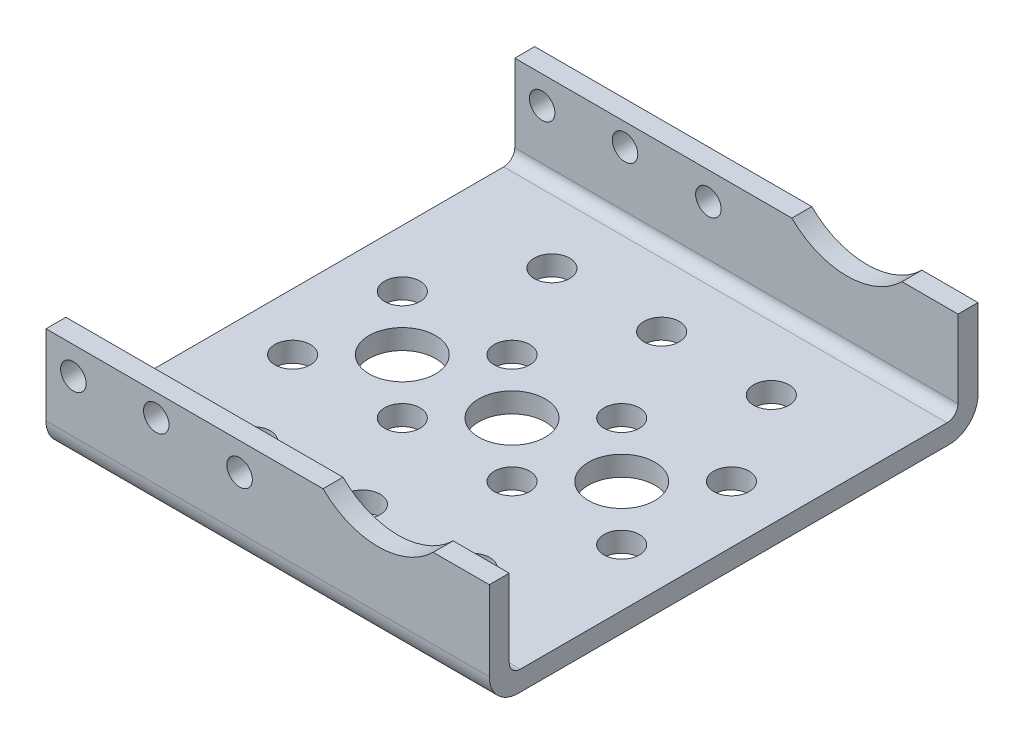
SolidWorks part; units mm, degrees
ref_plane "Front Plane" through (0, 0, 0) normal (0, 0, 1) x (1, 0, 0)
ref_plane "Top Plane" through (0, 0, 0) normal (0, 1, 0) x (1, 0, 0)
ref_plane "Right Plane" through (0, 0, 0) normal (1, 0, 0) x (0, 0, -1)
sketch "Model" plane through (0, 0, 0) normal (0, 0, 1) x (1, 0, 0)
  line L0 (23791.711, 2039.6293) -> (23791.711, 2044.2834)
  line L1 (23790.4383, 2043.5486) -> (23790.4383, 2039.0578)
  line L2 (23762.3662, 2020.5643) -> (23789.8726, 2036.445)
  line L3 (23789.7312, 2037.8331) -> (23762.5077, 2022.1157)
  line L4 (23781.1044, 2051.6318) -> (23764.4873, 2061.2254)
  line L5 (23790.6504, 2046.1205) -> (23788.1324, 2047.5742)
  line L6 (23779.8316, 2050.8969) -> (23763.2145, 2060.4906)
  line L7 (23789.3776, 2045.3857) -> (23786.8597, 2046.8394)
  line L8 (23790.4383, 2043.5486) -> (23791.711, 2044.2834)
  line L9 (23760.5278, 2026.2798) -> (23761.8006, 2027.0147)
  line L10 (23789.3776, 2045.3857) -> (23790.6504, 2046.1205)
  line L11 (23759.4671, 2028.117) -> (23760.7399, 2028.8518)
  line L12 (23786.8597, 2046.8394) -> (23788.1324, 2047.5742)
  line L13 (23756.9492, 2029.5706) -> (23758.222, 2030.3055)
  line L14 (23762.1539, 2055.3874) -> (23790.4383, 2039.0578)
  line L15 (23761.4468, 2054.1627) -> (23789.7312, 2037.8331)
  line L16 (23751.1939, 2034.363) -> (23749.9211, 2033.6282)
  line L17 (23781.1044, 2051.6318) -> (23779.8316, 2050.8969)
  line L18 (23762.1539, 2055.3874) -> (23762.1539, 2059.8782)
  line L19 (23761.8006, 2022.5239) -> (23761.8006, 2027.0147)
  line L20 (23760.5278, 2021.6258) -> (23760.5278, 2026.2798)
  line L21 (23739.1731, 2041.3031) -> (23761.4468, 2054.1627)
  line L22 (23763.2145, 2060.4906) -> (23764.4873, 2061.2254)
  line L23 (23733.304, 2043.2219) -> (23734.5768, 2043.9567)
  line L24 (23758.222, 2030.3055) -> (23760.7399, 2028.8518)
  line L25 (23734.5768, 2043.9567) -> (23751.1939, 2034.363)
  line L26 (23762.4645, 2060.5649) -> (23763.7373, 2061.2997)
  line L27 (23732.554, 2043.2961) -> (23733.8268, 2044.031)
  line L28 (23756.9492, 2029.5706) -> (23759.4671, 2028.117)
  line L29 (23733.304, 2043.2219) -> (23749.9211, 2033.6282)
  line L30 (23761.8006, 2022.5239) -> (23762.5077, 2022.1157)
  line L31 (23760.5278, 2021.6258) -> (23732.2434, 2037.9554)
  line L32 (23761.0663, 2020.4355) -> (23732.7819, 2036.7652)
  line L33 (23732.2434, 2037.9554) -> (23732.2434, 2042.6095)
  line L60 (23618.6723, 1978.7528) -> (23578.6723, 1978.7528)
  line L61 (23618.6723, 1976.1528) -> (23578.6723, 1976.1528)
  line L62 (23618.6723, 1978.7528) -> (23618.6723, 1934.6528)
  line L63 (23618.6723, 1937.2528) -> (23578.6723, 1937.2528)
  line L64 (23578.6723, 1934.6528) -> (23578.6723, 1978.7528)
  line L65 (23618.6723, 1934.6528) -> (23578.6723, 1934.6528)
  circle A21 centre (23588.7728, 1943.2028) radius 1.6
  circle A22 centre (23598.6723, 1943.2028) radius 1.6
  circle A23 centre (23608.5718, 1943.2028) radius 1.6
  circle A24 centre (23613.5215, 1951.7531) radius 1.6
  circle A25 centre (23603.622, 1951.7531) radius 1.6
  circle A26 centre (23593.7225, 1951.7531) radius 1.6
  circle A27 centre (23583.8231, 1951.7531) radius 1.6
  circle A28 centre (23583.8231, 1961.6526) radius 1.6
  circle A29 centre (23593.7225, 1961.6526) radius 1.6
  circle A30 centre (23603.622, 1961.6526) radius 1.6
  circle A31 centre (23613.5215, 1961.6526) radius 1.6
  circle A32 centre (23608.5718, 1970.2028) radius 1.6
  circle A33 centre (23598.6723, 1970.2028) radius 1.6
  circle A34 centre (23588.7728, 1970.2028) radius 1.6
  circle A35 centre (23588.7728, 1956.7028) radius 3
  circle A36 centre (23608.5718, 1956.7028) radius 3
  circle A37 centre (23598.6723, 1956.7028) radius 3
  spline S0 degree 3 poles (23760.8459, 2034.751) (23760.9643, 2034.8193) (23761.2325, 2034.93) (23761.6695, 2035.0174) (23762.1318, 2035.0302) (23762.5815, 2034.967) (23762.9823, 2034.8332) (23763.261, 2034.6635) (23763.4246, 2034.4993) (23763.5115, 2034.3715) (23763.565, 2034.2367) (23763.5772, 2034.1433) (23763.5772, 2034.0978) knots 0 0 0 0 0.128688 0.270271 0.417431 0.561777 0.695448 0.812714 0.864677 0.912512 0.95714 1 1 1 1
  spline S1 degree 3 poles (23746.3772, 2042.1805) (23746.3772, 2042.2415) (23746.3997, 2042.3685) (23746.496, 2042.5455) (23746.6482, 2042.7055) (23746.7756, 2042.7932) (23746.8458, 2042.8337) knots 0 0 0 0 0.217784 0.450913 0.710298 1 1 1 1
  spline S2 degree 3 poles (23770.3917, 2044.3037) (23770.5102, 2044.372) (23770.7783, 2044.4827) (23771.2154, 2044.5701) (23771.6776, 2044.5829) (23772.1274, 2044.5197) (23772.5282, 2044.3859) (23772.8069, 2044.2162) (23772.9705, 2044.052) (23773.0574, 2043.9242) (23773.1109, 2043.7894) (23773.1231, 2043.696) (23773.1231, 2043.6505) knots 0 0 0 0 0.128688 0.270271 0.417431 0.561777 0.695448 0.812714 0.864677 0.912512 0.95714 1 1 1 1
  spline S3 degree 3 poles (23788.0742, 2044.7771) (23788.0362, 2044.7552) (23787.9652, 2044.6956) (23787.8895, 2044.572) (23787.8446, 2044.4197) (23787.8358, 2044.3088) (23787.8358, 2044.2505) knots 0 0 0 0 0.217775 0.450893 0.710352 1 1 1 1
  spline S4 degree 3 poles (23753.8458, 2038.7923) (23753.9643, 2038.8607) (23754.2324, 2038.9714) (23754.6695, 2039.0588) (23755.1317, 2039.0716) (23755.5815, 2039.0084) (23755.9823, 2038.8745) (23756.261, 2038.7049) (23756.4246, 2038.5407) (23756.5115, 2038.4129) (23756.565, 2038.2781) (23756.5772, 2038.1847) (23756.5772, 2038.1392) knots 0 0 0 0 0.128688 0.270271 0.417431 0.561777 0.695448 0.812714 0.864677 0.912512 0.95714 1 1 1 1
  spline S5 degree 3 poles (23744.0215, 2035.6732) (23743.9835, 2035.6513) (23743.9125, 2035.5917) (23743.8368, 2035.4681) (23743.792, 2035.3158) (23743.7831, 2035.2049) (23743.7831, 2035.1466) knots 0 0 0 0 0.217775 0.450893 0.710352 1 1 1 1
  spline S6 degree 3 poles (23771.0985, 2035.3225) (23771.2302, 2035.2465) (23771.4691, 2035.082) (23771.7545, 2034.7823) (23771.9076, 2034.4998) (23771.9674, 2034.2695) (23771.9772, 2034.1546) (23771.9772, 2034.0978) knots 0 0 0 0 0.289555 0.548652 0.781634 0.891841 1 1 1 1
  spline S7 degree 3 poles (23758.1637, 2027.5084) (23758.1257, 2027.4865) (23758.0547, 2027.4269) (23757.979, 2027.3033) (23757.9342, 2027.151) (23757.9253, 2027.0401) (23757.9253, 2026.9818) knots 0 0 0 0 0.217775 0.450893 0.710352 1 1 1 1
  spline S8 degree 3 poles (23773.932, 2052.9419) (23773.894, 2052.92) (23773.823, 2052.8604) (23773.7473, 2052.7368) (23773.7024, 2052.5845) (23773.6936, 2052.4736) (23773.6936, 2052.4154) knots 0 0 0 0 0.217775 0.450893 0.710352 1 1 1 1
  spline S9 degree 3 poles (23746.8458, 2042.8337) (23746.9642, 2042.9021) (23747.2324, 2043.0127) (23747.6694, 2043.1002) (23748.1317, 2043.113) (23748.5815, 2043.0498) (23748.9822, 2042.9159) (23749.261, 2042.7463) (23749.4245, 2042.5821) (23749.5115, 2042.4543) (23749.565, 2042.3194) (23749.5772, 2042.2261) (23749.5772, 2042.1805) knots 0 0 0 0 0.128688 0.270271 0.417431 0.561777 0.695448 0.812714 0.864677 0.912512 0.95714 1 1 1 1
  spline S10 degree 3 poles (23753.3772, 2038.1392) (23753.3772, 2038.2001) (23753.3997, 2038.3271) (23753.496, 2038.5041) (23753.6483, 2038.6641) (23753.7756, 2038.7518) (23753.8458, 2038.7923) knots 0 0 0 0 0.217784 0.450913 0.710298 1 1 1 1
  spline S11 degree 3 poles (23763.3917, 2048.345) (23763.5101, 2048.4134) (23763.7783, 2048.5241) (23764.2153, 2048.6115) (23764.6776, 2048.6243) (23765.1274, 2048.5611) (23765.5281, 2048.4272) (23765.8069, 2048.2576) (23765.9704, 2048.0934) (23766.0574, 2047.9656) (23766.1109, 2047.8308) (23766.1231, 2047.7374) (23766.1231, 2047.6918) knots 0 0 0 0 0.128688 0.270271 0.417431 0.561777 0.695448 0.812714 0.864677 0.912512 0.95714 1 1 1 1
  spline S12 degree 3 poles (23760.3772, 2034.0978) (23760.3772, 2034.1587) (23760.3998, 2034.2857) (23760.4961, 2034.4627) (23760.6483, 2034.6227) (23760.7757, 2034.7104) (23760.8459, 2034.751) knots 0 0 0 0 0.217784 0.450913 0.710298 1 1 1 1
  spline S13 degree 3 poles (23739.8536, 2037.1593) (23739.8252, 2037.143) (23739.7627, 2037.1171) (23739.6596, 2037.102) (23739.5488, 2037.1102) (23739.3878, 2037.1531) (23739.1821, 2037.2656) (23738.9548, 2037.467) (23738.7538, 2037.7242) (23738.5957, 2038.0165) (23738.4931, 2038.3199) (23738.4656, 2038.5266) (23738.4656, 2038.6249) knots 0 0 0 0 0.042861 0.087494 0.135333 0.187304 0.304578 0.438252 0.582594 0.729744 0.871324 1 1 1 1
  spline S14 degree 3 poles (23733.4148, 2041.7968) (23733.3769, 2041.7749) (23733.3058, 2041.7153) (23733.2302, 2041.5917) (23733.1853, 2041.4394) (23733.1765, 2041.3285) (23733.1765, 2041.2702) knots 0 0 0 0 0.217775 0.450893 0.710352 1 1 1 1
  spline S15 degree 3 poles (23763.3253, 2059.0655) (23763.2874, 2059.0436) (23763.2163, 2058.984) (23763.1407, 2058.8604) (23763.0958, 2058.7081) (23763.0869, 2058.5973) (23763.0869, 2058.539) knots 0 0 0 0 0.217775 0.450893 0.710352 1 1 1 1
  spline S16 degree 3 poles (23786.8597, 2046.8394) (23786.744, 2046.7739) (23786.4986, 2046.6615) (23786.1022, 2046.5546) (23785.6799, 2046.5098) (23785.0726, 2046.5334) (23784.2661, 2046.7294) (23783.2983, 2047.1908) (23782.3352, 2047.8651) (23781.4109, 2048.7274) (23780.5586, 2049.7462) (23780.0613, 2050.5018) (23779.8316, 2050.8969) knots 0 0 0 0 0.045082 0.091075 0.138692 0.188569 0.296642 0.417359 0.550403 0.693911 0.844959 1 1 1 1
  spline S17 degree 3 poles (23769.7641, 2054.4281) (23769.7357, 2054.4117) (23769.6732, 2054.3858) (23769.57, 2054.3707) (23769.4593, 2054.3789) (23769.2983, 2054.4218) (23769.0926, 2054.5343) (23768.8652, 2054.7357) (23768.6643, 2054.9929) (23768.5062, 2055.2852) (23768.4036, 2055.5887) (23768.3761, 2055.7953) (23768.3761, 2055.8936) knots 0 0 0 0 0.042861 0.087494 0.135333 0.187304 0.304578 0.438252 0.582594 0.729744 0.871324 1 1 1 1
  spline S18 degree 3 poles (23763.2145, 2060.4906) (23763.1487, 2060.5286) (23763.0178, 2060.5909) (23762.8165, 2060.6395) (23762.6277, 2060.6347) (23762.514, 2060.5934) (23762.4645, 2060.5649) knots 0 0 0 0 0.289699 0.549083 0.782213 1 1 1 1
  spline S19 degree 3 poles (23767.3773, 2030.0564) (23767.3773, 2030.1173) (23767.3998, 2030.2444) (23767.4961, 2030.4213) (23767.6483, 2030.5813) (23767.7757, 2030.6691) (23767.8459, 2030.7096) knots 0 0 0 0 0.217784 0.450913 0.710298 1 1 1 1
  spline S20 degree 3 poles (23753.8458, 2046.8751) (23753.9642, 2046.9435) (23754.2324, 2047.0542) (23754.6694, 2047.1416) (23755.1317, 2047.1544) (23755.5814, 2047.0912) (23755.9822, 2046.9573) (23756.2609, 2046.7877) (23756.4245, 2046.6235) (23756.5114, 2046.4957) (23756.5649, 2046.3609) (23756.5772, 2046.2675) (23756.5772, 2046.2219) knots 0 0 0 0 0.128688 0.270271 0.417431 0.561777 0.695448 0.812714 0.864677 0.912512 0.95714 1 1 1 1
  spline S21 degree 3 poles (23762.9231, 2047.6918) (23762.9231, 2047.7528) (23762.9456, 2047.8798) (23763.0419, 2048.0568) (23763.1941, 2048.2168) (23763.3215, 2048.3045) (23763.3917, 2048.345) knots 0 0 0 0 0.217784 0.450913 0.710298 1 1 1 1
  spline S22 degree 3 poles (23758.9772, 2038.1391) (23758.9772, 2038.2245) (23759, 2038.3996) (23759.1004, 2038.6524) (23759.2634, 2038.892) (23759.4842, 2039.1138) (23759.7578, 2039.3138) (23760.1986, 2039.5534) (23760.8445, 2039.7691) (23761.6873, 2039.8875) (23762.5542, 2039.8635) (23763.3736, 2039.6996) (23763.8764, 2039.4921) (23764.0985, 2039.3639) knots 0 0 0 0 0.042846 0.087464 0.135285 0.187234 0.243726 0.304732 0.438366 0.582673 0.729791 0.871341 1 1 1 1
  spline S23 degree 3 poles (23790.4383, 2043.5486) (23790.4383, 2043.6324) (23790.4229, 2043.8069) (23790.3395, 2044.1651) (23790.1458, 2044.6045) (23789.8622, 2044.9919) (23789.5936, 2045.2432) (23789.4502, 2045.3438) (23789.3776, 2045.3857) knots 0 0 0 0 0.114224 0.237557 0.500001 0.762445 0.885777 1 1 1 1
  spline S24 degree 3 poles (23764.0985, 2039.3639) (23764.2302, 2039.2879) (23764.469, 2039.1234) (23764.7544, 2038.8237) (23764.9076, 2038.5412) (23764.9673, 2038.3109) (23764.9772, 2038.196) (23764.9772, 2038.1392) knots 0 0 0 0 0.289555 0.548652 0.781634 0.891841 1 1 1 1
  spline S25 degree 3 poles (23768.3761, 2055.8936) (23768.3761, 2055.9519) (23768.385, 2056.0627) (23768.4299, 2056.215) (23768.5055, 2056.3386) (23768.5766, 2056.3982) (23768.6145, 2056.4201) knots 0 0 0 0 0.289648 0.549107 0.782225 1 1 1 1
  spline S26 degree 3 poles (23769.9231, 2043.6505) (23769.9231, 2043.7114) (23769.9456, 2043.8384) (23770.0419, 2044.0154) (23770.1942, 2044.1754) (23770.3215, 2044.2631) (23770.3917, 2044.3037) knots 0 0 0 0 0.217784 0.450913 0.710298 1 1 1 1
  spline S27 degree 3 poles (23765.9773, 2034.0978) (23765.9773, 2034.1832) (23766.0001, 2034.3582) (23766.1005, 2034.611) (23766.2634, 2034.8507) (23766.4842, 2035.0724) (23766.7578, 2035.2724) (23767.1986, 2035.512) (23767.8445, 2035.7278) (23768.6873, 2035.8461) (23769.5542, 2035.8221) (23770.3736, 2035.6582) (23770.8765, 2035.4507) (23771.0985, 2035.3225) knots 0 0 0 0 0.042846 0.087464 0.135285 0.187234 0.243726 0.304732 0.438366 0.582673 0.729791 0.871341 1 1 1 1
  spline S28 degree 3 poles (23787.8358, 2044.2505) (23787.8358, 2044.1523) (23787.8633, 2043.9456) (23787.9659, 2043.6422) (23788.124, 2043.3499) (23788.3249, 2043.0927) (23788.5522, 2042.8913) (23788.758, 2042.7787) (23788.9189, 2042.7359) (23789.0297, 2042.7277) (23789.1329, 2042.7427) (23789.1954, 2042.7687) (23789.2237, 2042.785) knots 0 0 0 0 0.128676 0.270256 0.417406 0.561748 0.695422 0.812696 0.864667 0.912506 0.957139 1 1 1 1
  spline S29 degree 3 poles (23760.8458, 2042.8338) (23760.9642, 2042.9021) (23761.2324, 2043.0128) (23761.6694, 2043.1002) (23762.1317, 2043.113) (23762.5815, 2043.0498) (23762.9822, 2042.916) (23763.261, 2042.7463) (23763.4245, 2042.5821) (23763.5115, 2042.4543) (23763.565, 2042.3195) (23763.5772, 2042.2261) (23763.5772, 2042.1806) knots 0 0 0 0 0.128688 0.270271 0.417431 0.561777 0.695448 0.812714 0.864677 0.912512 0.95714 1 1 1 1
  spline S30 degree 3 poles (23773.6936, 2052.4154) (23773.6936, 2052.3171) (23773.7211, 2052.1104) (23773.8237, 2051.807) (23773.9818, 2051.5147) (23774.1827, 2051.2575) (23774.41, 2051.0561) (23774.6158, 2050.9436) (23774.7767, 2050.9007) (23774.8875, 2050.8925) (23774.9907, 2050.9076) (23775.0532, 2050.9335) (23775.0815, 2050.9498) knots 0 0 0 0 0.128676 0.270256 0.417406 0.561748 0.695422 0.812696 0.864667 0.912506 0.957139 1 1 1 1
  spline S31 degree 3 poles (23776.9231, 2039.6091) (23776.9231, 2039.67) (23776.9457, 2039.7971) (23777.042, 2039.974) (23777.1942, 2040.134) (23777.3216, 2040.2217) (23777.3918, 2040.2623) knots 0 0 0 0 0.217784 0.450913 0.710298 1 1 1 1
  spline S32 degree 3 poles (23751.9772, 2042.1805) (23751.9772, 2042.2659) (23752, 2042.441) (23752.1004, 2042.6938) (23752.2634, 2042.9334) (23752.4841, 2043.1552) (23752.7578, 2043.3551) (23753.1986, 2043.5948) (23753.8445, 2043.8105) (23754.6873, 2043.9289) (23755.5541, 2043.9049) (23756.3736, 2043.741) (23756.8764, 2043.5335) (23757.0985, 2043.4053) knots 0 0 0 0 0.042846 0.087464 0.135285 0.187234 0.243726 0.304732 0.438366 0.582673 0.729791 0.871341 1 1 1 1
  spline S33 degree 3 poles (23790.4383, 2039.0578) (23790.4383, 2038.9419) (23790.3948, 2038.6974) (23790.2432, 2038.3539) (23790.0215, 2038.0509) (23789.8315, 2037.891) (23789.7312, 2037.8331) knots 0 0 0 0 0.237239 0.500002 0.762764 1 1 1 1
  spline S34 degree 3 poles (23762.5077, 2022.1157) (23762.4638, 2022.0903) (23762.3765, 2022.0488) (23762.2423, 2022.0164) (23762.1164, 2022.0196) (23762.0406, 2022.0471) (23762.0077, 2022.0661) knots 0 0 0 0 0.2897 0.549084 0.782214 1 1 1 1
  spline S35 degree 3 poles (23774.3772, 2034.0978) (23774.3772, 2034.1588) (23774.3998, 2034.2858) (23774.4961, 2034.4628) (23774.6483, 2034.6227) (23774.7757, 2034.7105) (23774.8459, 2034.751) knots 0 0 0 0 0.217784 0.450913 0.710298 1 1 1 1
  spline S36 degree 3 poles (23760.5278, 2026.2798) (23760.5278, 2026.3637) (23760.5124, 2026.5382) (23760.429, 2026.8964) (23760.2353, 2027.3357) (23759.9517, 2027.7232) (23759.6831, 2027.9745) (23759.5397, 2028.075) (23759.4671, 2028.117) knots 0 0 0 0 0.114224 0.237557 0.500001 0.762445 0.885777 1 1 1 1
  spline S37 degree 3 poles (23756.9492, 2029.5706) (23756.8335, 2029.5052) (23756.5881, 2029.3928) (23756.1917, 2029.2859) (23755.7694, 2029.2411) (23755.1621, 2029.2646) (23754.3556, 2029.4607) (23753.3878, 2029.9221) (23752.4247, 2030.5963) (23751.5005, 2031.4587) (23750.6481, 2032.4775) (23750.1508, 2033.2331) (23749.9211, 2033.6282) knots 0 0 0 0 0.045082 0.091074 0.138691 0.188569 0.296642 0.417359 0.550403 0.693912 0.844959 1 1 1 1
  spline S38 degree 3 poles (23733.304, 2043.2219) (23733.2382, 2043.2599) (23733.1073, 2043.3222) (23732.906, 2043.3708) (23732.7172, 2043.366) (23732.6035, 2043.3247) (23732.554, 2043.2961) knots 0 0 0 0 0.289699 0.549083 0.782213 1 1 1 1
  spline S39 degree 3 poles (23738.4656, 2038.6249) (23738.4656, 2038.6831) (23738.4745, 2038.794) (23738.5194, 2038.9463) (23738.595, 2039.0699) (23738.6661, 2039.1295) (23738.704, 2039.1514) knots 0 0 0 0 0.289648 0.549107 0.782225 1 1 1 1
  spline S40 degree 3 poles (23757.9253, 2026.9818) (23757.9253, 2026.8835) (23757.9528, 2026.6769) (23758.0554, 2026.3735) (23758.2135, 2026.0812) (23758.4144, 2025.8239) (23758.6417, 2025.6226) (23758.8475, 2025.51) (23759.0084, 2025.4672) (23759.1192, 2025.4589) (23759.2224, 2025.474) (23759.2849, 2025.4999) (23759.3132, 2025.5163) knots 0 0 0 0 0.128676 0.270256 0.417406 0.561748 0.695422 0.812696 0.864667 0.912506 0.957139 1 1 1 1
  spline S41 degree 3 poles (23743.7831, 2035.1466) (23743.7831, 2035.0484) (23743.8106, 2034.8417) (23743.9132, 2034.5383) (23744.0713, 2034.246) (23744.2722, 2033.9888) (23744.4995, 2033.7874) (23744.7053, 2033.6748) (23744.8662, 2033.632) (23744.977, 2033.6238) (23745.0802, 2033.6388) (23745.1427, 2033.6648) (23745.1711, 2033.6811) knots 0 0 0 0 0.128676 0.270256 0.417406 0.561748 0.695422 0.812696 0.864667 0.912506 0.957139 1 1 1 1
  spline S42 degree 3 poles (23733.1765, 2041.2702) (23733.1765, 2041.172) (23733.2039, 2040.9653) (23733.3065, 2040.6619) (23733.4647, 2040.3696) (23733.6656, 2040.1124) (23733.8929, 2039.911) (23734.0986, 2039.7984) (23734.2596, 2039.7556) (23734.3704, 2039.7474) (23734.4735, 2039.7624) (23734.5361, 2039.7884) (23734.5644, 2039.8047) knots 0 0 0 0 0.128676 0.270256 0.417406 0.561748 0.695422 0.812696 0.864667 0.912506 0.957139 1 1 1 1
  spline S43 degree 3 poles (23763.0869, 2058.539) (23763.0869, 2058.4407) (23763.1144, 2058.2341) (23763.217, 2057.9306) (23763.3751, 2057.6383) (23763.5761, 2057.3811) (23763.8034, 2057.1797) (23764.0091, 2057.0672) (23764.1701, 2057.0243) (23764.2809, 2057.0161) (23764.384, 2057.0312) (23764.4465, 2057.0571) (23764.4749, 2057.0735) knots 0 0 0 0 0.128676 0.270256 0.417406 0.561748 0.695422 0.812696 0.864667 0.912506 0.957139 1 1 1 1
  spline S44 degree 3 poles (23767.8458, 2038.7924) (23767.9643, 2038.8608) (23768.2324, 2038.9714) (23768.6695, 2039.0588) (23769.1317, 2039.0716) (23769.5815, 2039.0084) (23769.9823, 2038.8746) (23770.261, 2038.7049) (23770.4246, 2038.5407) (23770.5115, 2038.4129) (23770.565, 2038.2781) (23770.5772, 2038.1847) (23770.5772, 2038.1392) knots 0 0 0 0 0.128688 0.270271 0.417431 0.561777 0.695448 0.812714 0.864677 0.912512 0.95714 1 1 1 1
  spline S45 degree 3 poles (23767.3772, 2038.1392) (23767.3772, 2038.2001) (23767.3997, 2038.3272) (23767.496, 2038.5041) (23767.6483, 2038.6641) (23767.7756, 2038.7518) (23767.8458, 2038.7924) knots 0 0 0 0 0.217784 0.450913 0.710298 1 1 1 1
  spline S46 degree 3 poles (23760.5278, 2021.6258) (23760.5278, 2021.494) (23760.5477, 2021.2435) (23760.6492, 2020.8993) (23760.82, 2020.6199) (23760.9805, 2020.4851) (23761.0663, 2020.4355) knots 0 0 0 0 0.289773 0.549065 0.782224 1 1 1 1
  spline S47 degree 3 poles (23760.3772, 2042.1806) (23760.3772, 2042.2415) (23760.3997, 2042.3685) (23760.496, 2042.5455) (23760.6482, 2042.7055) (23760.7756, 2042.7932) (23760.8458, 2042.8338) knots 0 0 0 0 0.217784 0.450913 0.710298 1 1 1 1
  spline S48 degree 3 poles (23745.6265, 2037.5861) (23745.7973, 2037.574) (23746.1213, 2037.5207) (23746.4933, 2037.3746) (23746.7325, 2037.214) (23746.8703, 2037.0826) (23746.9695, 2036.9388) (23747.0083, 2036.8338) (23747.0193, 2036.782) knots 0 0 0 0 0.301153 0.573738 0.695218 0.805891 0.906674 1 1 1 1
  spline S49 degree 3 poles (23774.8459, 2034.751) (23774.9643, 2034.8194) (23775.2325, 2034.93) (23775.6695, 2035.0175) (23776.1318, 2035.0303) (23776.5815, 2034.9671) (23776.9823, 2034.8332) (23777.261, 2034.6635) (23777.4246, 2034.4994) (23777.5115, 2034.3716) (23777.565, 2034.2367) (23777.5772, 2034.1434) (23777.5772, 2034.0978) knots 0 0 0 0 0.128688 0.270271 0.417431 0.561777 0.695448 0.812714 0.864677 0.912512 0.95714 1 1 1 1
  spline S50 degree 3 poles (23751.7739, 2033.4701) (23751.8985, 2033.5025) (23752.157, 2033.5474) (23752.5501, 2033.5585) (23752.9363, 2033.5142) (23753.2927, 2033.4174) (23753.5987, 2033.2732) (23753.837, 2033.0891) (23753.9705, 2032.9017) (23754.0227, 2032.7448) (23754.0313, 2032.6664) (23754.0313, 2032.6279) knots 0 0 0 0 0.144199 0.292657 0.439268 0.578198 0.704655 0.81588 0.912429 0.95686 1 1 1 1
  spline S51 degree 3 poles (23757.0985, 2043.4053) (23757.2302, 2043.3293) (23757.469, 2043.1647) (23757.7544, 2042.8651) (23757.9076, 2042.5826) (23757.9673, 2042.3523) (23757.9772, 2042.2374) (23757.9772, 2042.1806) knots 0 0 0 0 0.289555 0.548652 0.781634 0.891841 1 1 1 1
  spline S52 degree 3 poles (23753.3772, 2046.2219) (23753.3772, 2046.2829) (23753.3997, 2046.4099) (23753.496, 2046.5869) (23753.6482, 2046.7469) (23753.7756, 2046.8346) (23753.8458, 2046.8751) knots 0 0 0 0 0.217784 0.450913 0.710298 1 1 1 1
  spline S53 degree 3 poles (23760.8961, 2028.9582) (23760.9315, 2028.9116) (23760.9907, 2028.8139) (23761.0213, 2028.7032) (23761.0277, 2028.6491) knots 0 0 0 0 0.517744 1 1 1 1
  spline S54 degree 3 poles (23759.6265, 2029.5033) (23759.7608, 2029.4938) (23760.0201, 2029.4562) (23760.3786, 2029.3433) (23760.6778, 2029.1819) (23760.8365, 2029.0365) (23760.8961, 2028.9582) knots 0 0 0 0 0.285068 0.552072 0.791759 1 1 1 1
  spline S55 degree 3 poles (23777.3918, 2040.2623) (23777.5102, 2040.3307) (23777.7784, 2040.4413) (23778.2154, 2040.5287) (23778.6777, 2040.5415) (23779.1274, 2040.4783) (23779.5282, 2040.3445) (23779.8069, 2040.1748) (23779.9705, 2040.0106) (23780.0574, 2039.8828) (23780.1109, 2039.748) (23780.1231, 2039.6546) (23780.1231, 2039.6091) knots 0 0 0 0 0.128688 0.270271 0.417431 0.561777 0.695448 0.812714 0.864677 0.912512 0.95714 1 1 1 1
  spline S56 degree 3 poles (23767.8459, 2030.7096) (23767.9643, 2030.778) (23768.2325, 2030.8886) (23768.6695, 2030.976) (23769.1318, 2030.9888) (23769.5815, 2030.9256) (23769.9823, 2030.7918) (23770.2611, 2030.6221) (23770.4246, 2030.458) (23770.5115, 2030.3301) (23770.5651, 2030.1953) (23770.5773, 2030.102) (23770.5773, 2030.0564) knots 0 0 0 0 0.128688 0.270271 0.417431 0.561777 0.695448 0.812714 0.864677 0.912512 0.95714 1 1 1 1
  spline S57 degree 3 poles (23745.1711, 2033.6811) (23745.209, 2033.703) (23745.2801, 2033.7626) (23745.3557, 2033.8862) (23745.4006, 2034.0385) (23745.4094, 2034.1494) (23745.4094, 2034.2077) knots 0 0 0 0 0.217775 0.450893 0.710352 1 1 1 1
  spline S58 degree 3 poles (23775.0815, 2050.9498) (23775.1195, 2050.9717) (23775.1906, 2051.0313) (23775.2662, 2051.155) (23775.3111, 2051.3073) (23775.3199, 2051.4181) (23775.3199, 2051.4764) knots 0 0 0 0 0.217775 0.450893 0.710352 1 1 1 1
  spline S59 degree 3 poles (23789.2237, 2042.785) (23789.2617, 2042.8069) (23789.3328, 2042.8665) (23789.4084, 2042.9901) (23789.4533, 2043.1424) (23789.4621, 2043.2533) (23789.4621, 2043.3116) knots 0 0 0 0 0.217775 0.450893 0.710352 1 1 1 1
  spline S60 degree 3 poles (23734.5644, 2039.8047) (23734.6024, 2039.8266) (23734.6734, 2039.8862) (23734.7491, 2040.0098) (23734.7939, 2040.1621) (23734.8028, 2040.273) (23734.8028, 2040.3313) knots 0 0 0 0 0.217775 0.450893 0.710352 1 1 1 1
  spline S61 degree 3 poles (23759.3132, 2025.5163) (23759.3512, 2025.5382) (23759.4223, 2025.5978) (23759.4979, 2025.7214) (23759.5428, 2025.8737) (23759.5516, 2025.9846) (23759.5516, 2026.0429) knots 0 0 0 0 0.217775 0.450893 0.710352 1 1 1 1
  spline S62 degree 3 poles (23738.704, 2039.1514) (23738.7324, 2039.1678) (23738.7949, 2039.1937) (23738.8981, 2039.2088) (23739.0088, 2039.2006) (23739.1698, 2039.1577) (23739.3756, 2039.0451) (23739.6029, 2038.8438) (23739.8038, 2038.5865) (23739.9619, 2038.2942) (23740.0645, 2037.9908) (23740.092, 2037.7842) (23740.092, 2037.6859) knots 0 0 0 0 0.042861 0.087494 0.135333 0.187304 0.304578 0.438252 0.582594 0.729744 0.871324 1 1 1 1
  spline S63 degree 3 poles (23764.4749, 2057.0735) (23764.5129, 2057.0954) (23764.5839, 2057.155) (23764.6595, 2057.2786) (23764.7044, 2057.4309) (23764.7133, 2057.5417) (23764.7133, 2057.6) knots 0 0 0 0 0.217775 0.450893 0.710352 1 1 1 1
  spline S64 degree 3 poles (23768.6145, 2056.4201) (23768.6429, 2056.4365) (23768.7054, 2056.4624) (23768.8086, 2056.4775) (23768.9193, 2056.4693) (23769.0803, 2056.4264) (23769.286, 2056.3139) (23769.5134, 2056.1125) (23769.7143, 2055.8553) (23769.8724, 2055.563) (23769.975, 2055.2595) (23770.0025, 2055.0529) (23770.0025, 2054.9546) knots 0 0 0 0 0.042861 0.087494 0.135333 0.187304 0.304578 0.438252 0.582594 0.729744 0.871324 1 1 1 1
  spline S65 degree 3 poles (23732.7819, 2036.7652) (23732.6961, 2036.8147) (23732.5356, 2036.9496) (23732.3648, 2037.2289) (23732.2633, 2037.5731) (23732.2434, 2037.8236) (23732.2434, 2037.9554) knots 0 0 0 0 0.217776 0.450935 0.710227 1 1 1 1
  spline S66 degree 3 poles (23761.0663, 2020.4355) (23761.152, 2020.386) (23761.3491, 2020.3145) (23761.6764, 2020.3062) (23762.0252, 2020.3904) (23762.2521, 2020.4984) (23762.3662, 2020.5643) knots 0 0 0 0 0.217778 0.450937 0.710229 1 1 1 1
  spline S67 degree 3 poles (23762.0077, 2022.0661) (23761.9747, 2022.0852) (23761.913, 2022.1371) (23761.8473, 2022.2445) (23761.8082, 2022.3769) (23761.8006, 2022.4732) (23761.8006, 2022.5239) knots 0 0 0 0 0.217785 0.450914 0.710299 1 1 1 1
  spline S68 degree 3 poles (23764.69, 2037.409) (23764.6524, 2037.455) (23764.4793, 2037.644) (23764.2686, 2037.796) (23764.0985, 2037.8942) knots 0 0 0 0 0.232466 1 1 1 1
  spline S69 degree 3 poles (23764.9772, 2038.1392) (23764.9772, 2038.0538) (23764.9544, 2037.8787) (23764.854, 2037.6259) (23764.691, 2037.3863) (23764.4702, 2037.1645) (23764.1966, 2036.9646) (23763.7558, 2036.725) (23763.1099, 2036.5092) (23762.2671, 2036.3909) (23761.4002, 2036.4148) (23760.5808, 2036.5788) (23760.078, 2036.7862) (23759.8559, 2036.9144) knots 0 0 0 0 0.042846 0.087464 0.135285 0.187234 0.243726 0.304732 0.438366 0.582673 0.729791 0.871341 1 1 1 1
  spline S70 degree 3 poles (23766.1231, 2047.6918) (23766.1231, 2047.6309) (23766.1006, 2047.5039) (23766.0043, 2047.3269) (23765.852, 2047.1669) (23765.7247, 2047.0792) (23765.6545, 2047.0387) knots 0 0 0 0 0.217784 0.450913 0.710298 1 1 1 1
  spline S71 degree 3 poles (23771.69, 2033.3676) (23771.6524, 2033.4137) (23771.4793, 2033.6026) (23771.2686, 2033.7546) (23771.0985, 2033.8528) knots 0 0 0 0 0.232466 1 1 1 1
  spline S72 degree 3 poles (23771.9772, 2034.0978) (23771.9772, 2034.0124) (23771.9544, 2033.8374) (23771.854, 2033.5846) (23771.6911, 2033.3449) (23771.4703, 2033.1232) (23771.1966, 2032.9232) (23770.7558, 2032.6836) (23770.11, 2032.4678) (23769.2672, 2032.3495) (23768.4003, 2032.3734) (23767.5808, 2032.5374) (23767.078, 2032.7448) (23766.8559, 2032.8731) knots 0 0 0 0 0.042846 0.087464 0.135285 0.187234 0.243726 0.304732 0.438366 0.582673 0.729791 0.871341 1 1 1 1
  spline S73 degree 3 poles (23773.1231, 2043.6505) (23773.1231, 2043.5895) (23773.1006, 2043.4625) (23773.0043, 2043.2855) (23772.8521, 2043.1255) (23772.7247, 2043.0378) (23772.6545, 2042.9973) knots 0 0 0 0 0.217784 0.450913 0.710298 1 1 1 1
  spline S74 degree 3 poles (23757.69, 2041.4504) (23757.6523, 2041.4964) (23757.4793, 2041.6854) (23757.2685, 2041.8374) (23757.0985, 2041.9356) knots 0 0 0 0 0.232466 1 1 1 1
  spline S75 degree 3 poles (23757.9772, 2042.1806) (23757.9772, 2042.0952) (23757.9543, 2041.9201) (23757.8539, 2041.6673) (23757.691, 2041.4277) (23757.4702, 2041.2059) (23757.1966, 2041.006) (23756.7558, 2040.7663) (23756.1099, 2040.5506) (23755.2671, 2040.4322) (23754.4002, 2040.4562) (23753.5808, 2040.6201) (23753.0779, 2040.8276) (23752.8559, 2040.9558) knots 0 0 0 0 0.042846 0.087464 0.135285 0.187234 0.243726 0.304732 0.438366 0.582673 0.729791 0.871341 1 1 1 1
  spline S76 degree 3 poles (23780.1231, 2039.6091) (23780.1231, 2039.5482) (23780.1006, 2039.4211) (23780.0043, 2039.2441) (23779.8521, 2039.0842) (23779.7247, 2038.9964) (23779.6545, 2038.9559) knots 0 0 0 0 0.217784 0.450913 0.710298 1 1 1 1
  spline S77 degree 3 poles (23761.4468, 2054.1627) (23761.5472, 2054.2206) (23761.7371, 2054.3805) (23761.9589, 2054.6835) (23762.1104, 2055.027) (23762.1539, 2055.2715) (23762.1539, 2055.3874) knots 0 0 0 0 0.237236 0.499998 0.762761 1 1 1 1
  spline S78 degree 3 poles (23740.092, 2037.6859) (23740.092, 2037.6276) (23740.0831, 2037.5168) (23740.0382, 2037.3644) (23739.9626, 2037.2408) (23739.8915, 2037.1812) (23739.8536, 2037.1593) knots 0 0 0 0 0.289648 0.549107 0.782225 1 1 1 1
  spline S79 degree 3 poles (23759.5516, 2026.0429) (23759.5516, 2026.1411) (23759.5242, 2026.3478) (23759.4216, 2026.6512) (23759.2634, 2026.9435) (23759.0625, 2027.2007) (23758.8352, 2027.4021) (23758.6295, 2027.5147) (23758.4685, 2027.5575) (23758.3577, 2027.5657) (23758.2546, 2027.5507) (23758.192, 2027.5247) (23758.1637, 2027.5084) knots 0 0 0 0 0.128676 0.270256 0.417406 0.561748 0.695422 0.812696 0.864667 0.912506 0.957139 1 1 1 1
  spline S80 degree 3 poles (23745.4094, 2034.2077) (23745.4094, 2034.306) (23745.382, 2034.5126) (23745.2794, 2034.816) (23745.1212, 2035.1083) (23744.9203, 2035.3656) (23744.693, 2035.5669) (23744.4873, 2035.6795) (23744.3263, 2035.7223) (23744.2155, 2035.7306) (23744.1124, 2035.7155) (23744.0498, 2035.6896) (23744.0215, 2035.6732) knots 0 0 0 0 0.128676 0.270256 0.417406 0.561748 0.695422 0.812696 0.864667 0.912506 0.957139 1 1 1 1
  spline S81 degree 3 poles (23734.8028, 2040.3313) (23734.8028, 2040.4296) (23734.7753, 2040.6362) (23734.6727, 2040.9396) (23734.5146, 2041.2319) (23734.3137, 2041.4892) (23734.0864, 2041.6905) (23733.8806, 2041.8031) (23733.7197, 2041.846) (23733.6089, 2041.8542) (23733.5057, 2041.8391) (23733.4432, 2041.8132) (23733.4148, 2041.7968) knots 0 0 0 0 0.128676 0.270256 0.417406 0.561748 0.695422 0.812696 0.864667 0.912506 0.957139 1 1 1 1
  spline S82 degree 3 poles (23753.0164, 2032.0179) (23753.049, 2032.0105) (23753.1748, 2031.9792) (23753.298, 2031.9372) (23753.3864, 2031.8993) knots 0 0 0 0 0.258186 1 1 1 1
  spline S83 degree 3 poles (23777.5772, 2034.0978) (23777.5772, 2034.0369) (23777.5547, 2033.9099) (23777.4584, 2033.7329) (23777.3062, 2033.5729) (23777.1788, 2033.4852) (23777.1086, 2033.4446) knots 0 0 0 0 0.217784 0.450913 0.710298 1 1 1 1
  spline S84 degree 3 poles (23768.0222, 2029.3278) (23768.1668, 2029.3899) (23768.4826, 2029.4812) (23768.9774, 2029.5256) (23769.472, 2029.4811) (23769.7878, 2029.3899) (23769.9324, 2029.3278) knots 0 0 0 0 0.241562 0.500041 0.758525 1 1 1 1
  spline S85 degree 3 poles (23761.0222, 2033.3692) (23761.1668, 2033.4313) (23761.4826, 2033.5226) (23761.9773, 2033.567) (23762.472, 2033.5225) (23762.7878, 2033.4313) (23762.9323, 2033.3692) knots 0 0 0 0 0.241562 0.500041 0.758525 1 1 1 1
  spline S86 degree 3 poles (23770.5772, 2038.1392) (23770.5772, 2038.0782) (23770.5547, 2037.9512) (23770.4584, 2037.7742) (23770.3062, 2037.6143) (23770.1788, 2037.5265) (23770.1086, 2037.486) knots 0 0 0 0 0.217784 0.450913 0.710298 1 1 1 1
  spline S87 degree 3 poles (23754.0221, 2037.4105) (23754.1667, 2037.4727) (23754.4826, 2037.5639) (23754.9773, 2037.6083) (23755.472, 2037.5639) (23755.7878, 2037.4727) (23755.9323, 2037.4106) knots 0 0 0 0 0.241562 0.500041 0.758525 1 1 1 1
  spline S88 degree 3 poles (23747.0221, 2041.4519) (23747.1667, 2041.514) (23747.4825, 2041.6053) (23747.9773, 2041.6497) (23748.4719, 2041.6053) (23748.7877, 2041.514) (23748.9323, 2041.4519) knots 0 0 0 0 0.241562 0.500041 0.758525 1 1 1 1
  spline S89 degree 3 poles (23754.0221, 2045.4933) (23754.1667, 2045.5554) (23754.4825, 2045.6467) (23754.9772, 2045.6911) (23755.4719, 2045.6467) (23755.7877, 2045.5554) (23755.9322, 2045.4933) knots 0 0 0 0 0.241562 0.500041 0.758525 1 1 1 1
  spline S90 degree 3 poles (23763.5772, 2042.1806) (23763.5772, 2042.1196) (23763.5547, 2041.9926) (23763.4584, 2041.8156) (23763.3061, 2041.6556) (23763.1788, 2041.5679) (23763.1086, 2041.5274) knots 0 0 0 0 0.217784 0.450913 0.710298 1 1 1 1
  spline S91 degree 3 poles (23761.0221, 2041.452) (23761.1667, 2041.5141) (23761.4825, 2041.6054) (23761.9773, 2041.6497) (23762.4719, 2041.6053) (23762.7877, 2041.5141) (23762.9323, 2041.452) knots 0 0 0 0 0.241562 0.500041 0.758525 1 1 1 1
  spline S92 degree 3 poles (23768.0221, 2037.4106) (23768.1667, 2037.4727) (23768.4826, 2037.564) (23768.9773, 2037.6084) (23769.472, 2037.5639) (23769.7878, 2037.4727) (23769.9323, 2037.4106) knots 0 0 0 0 0.241562 0.500041 0.758525 1 1 1 1
  spline S93 degree 3 poles (23775.0222, 2033.3692) (23775.1668, 2033.4313) (23775.4826, 2033.5226) (23775.9773, 2033.567) (23776.472, 2033.5226) (23776.7878, 2033.4313) (23776.9323, 2033.3692) knots 0 0 0 0 0.241562 0.500041 0.758525 1 1 1 1
  spline S94 degree 3 poles (23756.5772, 2046.2219) (23756.5771, 2046.161) (23756.5546, 2046.034) (23756.4583, 2045.857) (23756.3061, 2045.697) (23756.1787, 2045.6093) (23756.1085, 2045.5688) knots 0 0 0 0 0.217784 0.450913 0.710298 1 1 1 1
  spline S95 degree 3 poles (23777.5681, 2038.8805) (23777.7127, 2038.9426) (23778.0285, 2039.0339) (23778.5232, 2039.0783) (23779.0179, 2039.0338) (23779.3337, 2038.9426) (23779.4782, 2038.8805) knots 0 0 0 0 0.241562 0.500041 0.758525 1 1 1 1
  spline S96 degree 3 poles (23770.568, 2042.9219) (23770.7126, 2042.984) (23771.0285, 2043.0753) (23771.5232, 2043.1196) (23772.0179, 2043.0752) (23772.3337, 2042.984) (23772.4782, 2042.9219) knots 0 0 0 0 0.241562 0.500041 0.758525 1 1 1 1
  spline S97 degree 3 poles (23763.568, 2046.9632) (23763.7126, 2047.0254) (23764.0284, 2047.1166) (23764.5232, 2047.161) (23765.0178, 2047.1166) (23765.3336, 2047.0253) (23765.4782, 2046.9632) knots 0 0 0 0 0.241562 0.500041 0.758525 1 1 1 1
  spline S98 degree 3 poles (23749.5772, 2042.1805) (23749.5772, 2042.1196) (23749.5547, 2041.9926) (23749.4584, 2041.8156) (23749.3061, 2041.6556) (23749.1788, 2041.5679) (23749.1086, 2041.5273) knots 0 0 0 0 0.217784 0.450913 0.710298 1 1 1 1
  spline S99 degree 3 poles (23756.5772, 2038.1392) (23756.5772, 2038.0782) (23756.5547, 2037.9512) (23756.4584, 2037.7742) (23756.3062, 2037.6142) (23756.1788, 2037.5265) (23756.1086, 2037.486) knots 0 0 0 0 0.217784 0.450913 0.710298 1 1 1 1
  spline S100 degree 3 poles (23764.0985, 2037.8942) (23763.9199, 2037.9973) (23763.523, 2038.1728) (23762.8746, 2038.3391) (23762.1768, 2038.4139) (23761.4682, 2038.3928) (23760.7875, 2038.2771) (23760.1715, 2038.0728) (23759.6535, 2037.7908) (23759.3736, 2037.5425) (23759.2644, 2037.409) knots 0 0 0 0 0.119612 0.249983 0.38689 0.525272 0.659905 0.78601 0.899935 1 1 1 1
  spline S101 degree 3 poles (23771.0985, 2033.8528) (23770.9199, 2033.9559) (23770.523, 2034.1314) (23769.8746, 2034.2978) (23769.1769, 2034.3725) (23768.4682, 2034.3514) (23767.7875, 2034.2357) (23767.1715, 2034.0314) (23766.6536, 2033.7494) (23766.3737, 2033.5011) (23766.2644, 2033.3676) knots 0 0 0 0 0.119612 0.249983 0.38689 0.525272 0.659905 0.78601 0.899935 1 1 1 1
  spline S102 degree 3 poles (23757.0985, 2041.9356) (23756.9199, 2042.0387) (23756.523, 2042.2142) (23755.8746, 2042.3805) (23755.1768, 2042.4553) (23754.4682, 2042.4342) (23753.7874, 2042.3185) (23753.1715, 2042.1142) (23752.6535, 2041.8322) (23752.3736, 2041.5839) (23752.2644, 2041.4503) knots 0 0 0 0 0.119612 0.249983 0.38689 0.525272 0.659905 0.78601 0.899935 1 1 1 1
  spline S103 degree 3 poles (23763.5772, 2034.0978) (23763.5772, 2034.0368) (23763.5547, 2033.9098) (23763.4584, 2033.7328) (23763.3062, 2033.5729) (23763.1788, 2033.4851) (23763.1086, 2033.4446) knots 0 0 0 0 0.217784 0.450913 0.710298 1 1 1 1
  spline S104 degree 3 poles (23770.5773, 2030.0564) (23770.5773, 2029.9955) (23770.5547, 2029.8684) (23770.4584, 2029.6915) (23770.3062, 2029.5315) (23770.1788, 2029.4437) (23770.1086, 2029.4032) knots 0 0 0 0 0.217784 0.450913 0.710298 1 1 1 1
  spline S105 degree 3 poles (23781.1044, 2051.6318) (23781.3341, 2051.2366) (23781.8314, 2050.4811) (23782.6837, 2049.4623) (23783.608, 2048.5999) (23784.5711, 2047.9256) (23785.5389, 2047.4643) (23786.3454, 2047.2682) (23786.9527, 2047.2447) (23787.3749, 2047.2895) (23787.7713, 2047.3963) (23788.0168, 2047.5088) (23788.1324, 2047.5742) knots 0 0 0 0 0.155041 0.306088 0.449597 0.582641 0.703358 0.811431 0.861309 0.908926 0.954918 1 1 1 1
  spline S106 degree 3 poles (23790.6504, 2046.1205) (23790.723, 2046.0786) (23790.8664, 2045.9781) (23791.1349, 2045.7268) (23791.4186, 2045.3393) (23791.6123, 2044.8999) (23791.6957, 2044.5417) (23791.711, 2044.3672) (23791.711, 2044.2834) knots 0 0 0 0 0.114223 0.237555 0.499999 0.762443 0.885776 1 1 1 1
  spline S107 degree 3 poles (23751.1939, 2034.363) (23751.4236, 2033.9679) (23751.9209, 2033.2123) (23752.7732, 2032.1936) (23753.6975, 2031.3312) (23754.6606, 2030.6569) (23755.6284, 2030.1955) (23756.4349, 2029.9995) (23757.0422, 2029.9759) (23757.4644, 2030.0208) (23757.8608, 2030.1276) (23758.1063, 2030.24) (23758.222, 2030.3055) knots 0 0 0 0 0.155041 0.306089 0.449597 0.582641 0.703358 0.811431 0.861308 0.908925 0.954918 1 1 1 1
  spline S108 degree 3 poles (23760.7399, 2028.8518) (23760.8125, 2028.8099) (23760.9559, 2028.7093) (23761.2245, 2028.458) (23761.5081, 2028.0706) (23761.7018, 2027.6312) (23761.7852, 2027.273) (23761.8006, 2027.0985) (23761.8006, 2027.0147) knots 0 0 0 0 0.114223 0.237555 0.499999 0.762443 0.885776 1 1 1 1
  spline S109 degree 3 poles (23754.0313, 2032.6279) (23754.0313, 2032.5669) (23754.0088, 2032.4399) (23753.9125, 2032.2629) (23753.7603, 2032.103) (23753.6329, 2032.0152) (23753.5627, 2031.9747) knots 0 0 0 0 0.217784 0.450913 0.710298 1 1 1 1
  spline S110 degree 3 poles (23732.554, 2043.2961) (23732.5046, 2043.2676) (23732.412, 2043.1898) (23732.3134, 2043.0286) (23732.2549, 2042.83) (23732.2434, 2042.6855) (23732.2434, 2042.6095) knots 0 0 0 0 0.217786 0.450916 0.7103 1 1 1 1
  spline S111 degree 3 poles (23733.8268, 2044.031) (23733.8763, 2044.0596) (23733.99, 2044.1008) (23734.1788, 2044.1056) (23734.3801, 2044.057) (23734.511, 2043.9947) (23734.5768, 2043.9567) knots 0 0 0 0 0.217787 0.450917 0.710301 1 1 1 1
  spline S112 degree 3 poles (23762.4645, 2060.5649) (23762.4151, 2060.5363) (23762.3225, 2060.4585) (23762.2239, 2060.2973) (23762.1654, 2060.0987) (23762.1539, 2059.9542) (23762.1539, 2059.8782) knots 0 0 0 0 0.217786 0.450916 0.7103 1 1 1 1
  spline S113 degree 3 poles (23763.7373, 2061.2997) (23763.7868, 2061.3283) (23763.9005, 2061.3695) (23764.0893, 2061.3743) (23764.2906, 2061.3257) (23764.4215, 2061.2634) (23764.4873, 2061.2254) knots 0 0 0 0 0.217787 0.450917 0.710301 1 1 1 1
  spline S114 degree 3 poles (23770.0025, 2054.9546) (23770.0025, 2054.8963) (23769.9936, 2054.7855) (23769.9487, 2054.6332) (23769.8731, 2054.5096) (23769.802, 2054.45) (23769.7641, 2054.4281) knots 0 0 0 0 0.289648 0.549107 0.782225 1 1 1 1
  spline S115 degree 3 poles (23789.4621, 2043.3116) (23789.4621, 2043.4099) (23789.4346, 2043.6165) (23789.332, 2043.9199) (23789.1739, 2044.2122) (23788.973, 2044.4695) (23788.7457, 2044.6708) (23788.54, 2044.7834) (23788.379, 2044.8263) (23788.2682, 2044.8345) (23788.165, 2044.8194) (23788.1025, 2044.7935) (23788.0742, 2044.7771) knots 0 0 0 0 0.128676 0.270256 0.417406 0.561748 0.695422 0.812696 0.864667 0.912506 0.957139 1 1 1 1
  spline S116 degree 3 poles (23775.3199, 2051.4764) (23775.3199, 2051.5747) (23775.2925, 2051.7813) (23775.1899, 2052.0847) (23775.0317, 2052.3771) (23774.8308, 2052.6343) (23774.6035, 2052.8356) (23774.3978, 2052.9482) (23774.2368, 2052.9911) (23774.126, 2052.9993) (23774.0229, 2052.9842) (23773.9603, 2052.9583) (23773.932, 2052.9419) knots 0 0 0 0 0.128676 0.270256 0.417406 0.561748 0.695422 0.812696 0.864667 0.912506 0.957139 1 1 1 1
  spline S117 degree 3 poles (23764.7133, 2057.6) (23764.7133, 2057.6983) (23764.6858, 2057.9049) (23764.5832, 2058.2084) (23764.4251, 2058.5007) (23764.2242, 2058.7579) (23763.9969, 2058.9593) (23763.7911, 2059.0718) (23763.6302, 2059.1147) (23763.5194, 2059.1229) (23763.4162, 2059.1078) (23763.3537, 2059.0819) (23763.3253, 2059.0655) knots 0 0 0 0 0.128676 0.270256 0.417406 0.561748 0.695422 0.812696 0.864667 0.912506 0.957139 1 1 1 1
  spline S118 degree 3 poles (23789.8726, 2036.445) (23789.9984, 2036.5177) (23790.247, 2036.6919) (23790.5891, 2037.0119) (23790.9043, 2037.3902) (23791.1808, 2037.8126) (23791.4083, 2038.2632) (23791.5783, 2038.7254) (23791.6844, 2039.1816) (23791.711, 2039.484) (23791.711, 2039.6293) knots 0 0 0 0 0.114144 0.237331 0.366973 0.499998 0.633024 0.762666 0.885855 1 1 1 1
  spline S119 degree 3 poles (23753.5627, 2031.9747) (23753.5358, 2031.9591) (23753.4208, 2031.8975) (23753.2988, 2031.8492) (23753.2042, 2031.819) knots 0 0 0 0 0.238433 1 1 1 1
  spline S120 degree 3 poles (23770.1086, 2029.4032) (23769.9902, 2029.3348) (23769.7221, 2029.2242) (23769.285, 2029.1368) (23768.8227, 2029.124) (23768.373, 2029.1872) (23767.9722, 2029.321) (23767.6935, 2029.4907) (23767.5299, 2029.6548) (23767.443, 2029.7827) (23767.3895, 2029.9175) (23767.3773, 2030.0109) (23767.3773, 2030.0564) knots 0 0 0 0 0.128688 0.270271 0.417431 0.561777 0.695448 0.812714 0.864677 0.912512 0.95714 1 1 1 1
  spline S121 degree 3 poles (23763.1086, 2033.4446) (23762.9902, 2033.3762) (23762.722, 2033.2656) (23762.285, 2033.1781) (23761.8227, 2033.1653) (23761.373, 2033.2285) (23760.9722, 2033.3624) (23760.6934, 2033.5321) (23760.5299, 2033.6962) (23760.443, 2033.824) (23760.3894, 2033.9589) (23760.3772, 2034.0522) (23760.3772, 2034.0978) knots 0 0 0 0 0.128688 0.270271 0.417431 0.561777 0.695448 0.812714 0.864677 0.912512 0.95714 1 1 1 1
  spline S122 degree 3 poles (23756.1086, 2037.486) (23755.9901, 2037.4176) (23755.722, 2037.3069) (23755.2849, 2037.2195) (23754.8227, 2037.2067) (23754.3729, 2037.2699) (23753.9722, 2037.4038) (23753.6934, 2037.5734) (23753.5298, 2037.7376) (23753.4429, 2037.8654) (23753.3894, 2038.0002) (23753.3772, 2038.0936) (23753.3772, 2038.1392) knots 0 0 0 0 0.128688 0.270271 0.417431 0.561777 0.695448 0.812714 0.864677 0.912512 0.95714 1 1 1 1
  spline S123 degree 3 poles (23749.1086, 2041.5273) (23748.9901, 2041.459) (23748.722, 2041.3483) (23748.2849, 2041.2609) (23747.8227, 2041.2481) (23747.3729, 2041.3113) (23746.9721, 2041.4451) (23746.6934, 2041.6148) (23746.5298, 2041.779) (23746.4429, 2041.9068) (23746.3894, 2042.0416) (23746.3772, 2042.135) (23746.3772, 2042.1805) knots 0 0 0 0 0.128688 0.270271 0.417431 0.561777 0.695448 0.812714 0.864677 0.912512 0.95714 1 1 1 1
  spline S124 degree 3 poles (23756.1085, 2045.5688) (23755.9901, 2045.5004) (23755.7219, 2045.3897) (23755.2849, 2045.3023) (23754.8226, 2045.2895) (23754.3729, 2045.3527) (23753.9721, 2045.4866) (23753.6934, 2045.6562) (23753.5298, 2045.8204) (23753.4429, 2045.9482) (23753.3894, 2046.083) (23753.3771, 2046.1764) (23753.3772, 2046.2219) knots 0 0 0 0 0.128688 0.270271 0.417431 0.561777 0.695448 0.812714 0.864677 0.912512 0.95714 1 1 1 1
  spline S125 degree 3 poles (23763.1086, 2041.5274) (23762.9901, 2041.459) (23762.722, 2041.3484) (23762.2849, 2041.2609) (23761.8227, 2041.2481) (23761.3729, 2041.3113) (23760.9721, 2041.4452) (23760.6934, 2041.6148) (23760.5298, 2041.779) (23760.4429, 2041.9068) (23760.3894, 2042.0417) (23760.3772, 2042.135) (23760.3772, 2042.1806) knots 0 0 0 0 0.128688 0.270271 0.417431 0.561777 0.695448 0.812714 0.864677 0.912512 0.95714 1 1 1 1
  spline S126 degree 3 poles (23770.1086, 2037.486) (23769.9901, 2037.4176) (23769.722, 2037.307) (23769.2849, 2037.2195) (23768.8227, 2037.2067) (23768.3729, 2037.2699) (23767.9722, 2037.4038) (23767.6934, 2037.5735) (23767.5298, 2037.7376) (23767.4429, 2037.8654) (23767.3894, 2038.0003) (23767.3772, 2038.0936) (23767.3772, 2038.1392) knots 0 0 0 0 0.128688 0.270271 0.417431 0.561777 0.695448 0.812714 0.864677 0.912512 0.95714 1 1 1 1
  spline S127 degree 3 poles (23777.1086, 2033.4446) (23776.9902, 2033.3762) (23776.722, 2033.2656) (23776.285, 2033.1782) (23775.8227, 2033.1654) (23775.373, 2033.2286) (23774.9722, 2033.3624) (23774.6934, 2033.5321) (23774.5299, 2033.6963) (23774.443, 2033.8241) (23774.3894, 2033.9589) (23774.3772, 2034.0523) (23774.3772, 2034.0978) knots 0 0 0 0 0.128688 0.270271 0.417431 0.561777 0.695448 0.812714 0.864677 0.912512 0.95714 1 1 1 1
  spline S128 degree 3 poles (23779.6545, 2038.9559) (23779.5361, 2038.8875) (23779.2679, 2038.7769) (23778.8309, 2038.6895) (23778.3686, 2038.6766) (23777.9189, 2038.7398) (23777.5181, 2038.8737) (23777.2393, 2039.0434) (23777.0758, 2039.2075) (23776.9889, 2039.3353) (23776.9353, 2039.4702) (23776.9231, 2039.5635) (23776.9231, 2039.6091) knots 0 0 0 0 0.128688 0.270271 0.417431 0.561777 0.695448 0.812714 0.864677 0.912512 0.95714 1 1 1 1
  spline S129 degree 3 poles (23772.6545, 2042.9973) (23772.536, 2042.9289) (23772.2679, 2042.8183) (23771.8308, 2042.7308) (23771.3686, 2042.718) (23770.9188, 2042.7812) (23770.5181, 2042.9151) (23770.2393, 2043.0847) (23770.0757, 2043.2489) (23769.9888, 2043.3767) (23769.9353, 2043.5116) (23769.9231, 2043.6049) (23769.9231, 2043.6505) knots 0 0 0 0 0.128688 0.270271 0.417431 0.561777 0.695448 0.812714 0.864677 0.912512 0.95714 1 1 1 1
  spline S130 degree 3 poles (23765.6545, 2047.0387) (23765.536, 2046.9703) (23765.2679, 2046.8596) (23764.8308, 2046.7722) (23764.3686, 2046.7594) (23763.9188, 2046.8226) (23763.518, 2046.9565) (23763.2393, 2047.1261) (23763.0757, 2047.2903) (23762.9888, 2047.4181) (23762.9353, 2047.5529) (23762.9231, 2047.6463) (23762.9231, 2047.6918) knots 0 0 0 0 0.128688 0.270271 0.417431 0.561777 0.695448 0.812714 0.864677 0.912512 0.95714 1 1 1 1
  spline S131 degree 3 poles (23759.8559, 2036.9144) (23759.7242, 2036.9905) (23759.4854, 2037.155) (23759.2, 2037.4547) (23759.0468, 2037.7371) (23758.9871, 2037.9675) (23758.9772, 2038.0824) (23758.9772, 2038.1391) knots 0 0 0 0 0.289555 0.548652 0.781634 0.891841 1 1 1 1
  spline S132 degree 3 poles (23766.8559, 2032.8731) (23766.7243, 2032.9491) (23766.4854, 2033.1136) (23766.2, 2033.4133) (23766.0469, 2033.6958) (23765.9871, 2033.9261) (23765.9773, 2034.041) (23765.9773, 2034.0978) knots 0 0 0 0 0.289555 0.548652 0.781634 0.891841 1 1 1 1
  spline S133 degree 3 poles (23752.8559, 2040.9558) (23752.7242, 2041.0318) (23752.4854, 2041.1964) (23752.2, 2041.496) (23752.0468, 2041.7785) (23751.9871, 2042.0088) (23751.9772, 2042.1237) (23751.9772, 2042.1805) knots 0 0 0 0 0.289555 0.548652 0.781634 0.891841 1 1 1 1
sketch "Sketch2" plane through (0, 0, 0) normal (0, 0, 1) x (1, 0, 0)
  line L0 (23578.6723, 2086.3771) -> (23618.6723, 2086.3771)
  line L1 (23618.6723, 2084.5771) -> (23578.6723, 2084.5771)
  line L2 (23578.6723, 2083.5771) -> (23618.6723, 2083.5771)
  line L3 (23618.6723, 2042.2771) -> (23618.6723, 2086.3771)
  line L4 (23617.1723, 2084.5771) -> (23617.1723, 2086.3771)
  line L5 (23617.1723, 2042.2771) -> (23617.1723, 2044.0771)
  line L6 (23613.6114, 2084.5771) -> (23613.6114, 2086.3771)
  line L7 (23613.6114, 2042.2771) -> (23613.6114, 2044.0771)
  line L8 (23603.6723, 2044.0771) -> (23603.6723, 2042.2771)
  line L9 (23603.6723, 2086.3771) -> (23603.6723, 2084.5771)
  line L10 (23578.6723, 2045.0771) -> (23618.6723, 2045.0771)
  line L11 (23580.1723, 2084.5771) -> (23580.1723, 2086.3771)
  line L12 (23580.1723, 2042.2771) -> (23580.1723, 2044.0771)
  line L13 (23578.6723, 2044.0771) -> (23618.6723, 2044.0771)
  line L14 (23578.6723, 2042.2771) -> (23578.6723, 2086.3771)
  line L15 (23578.6723, 2042.2771) -> (23618.6723, 2042.2771)
  circle A0 centre (23588.7728, 2050.8271) radius 1.6
  circle A1 centre (23598.6723, 2050.8271) radius 1.6
  circle A2 centre (23608.5718, 2050.8271) radius 1.6
  circle A3 centre (23613.5215, 2059.3774) radius 1.6
  circle A4 centre (23603.622, 2059.3774) radius 1.6
  circle A5 centre (23593.7225, 2059.3774) radius 1.6
  circle A6 centre (23583.8231, 2059.3774) radius 1.6
  circle A7 centre (23583.8231, 2069.2769) radius 1.6
  circle A8 centre (23593.7225, 2069.2769) radius 1.6
  circle A9 centre (23603.622, 2069.2769) radius 1.6
  circle A10 centre (23613.5215, 2069.2769) radius 1.6
  circle A11 centre (23608.5718, 2077.8271) radius 1.6
  circle A12 centre (23598.6723, 2077.8271) radius 1.6
  circle A13 centre (23588.7728, 2077.8271) radius 1.6
  circle A14 centre (23598.6723, 2064.3271) radius 3
  circle A15 centre (23608.5718, 2064.3271) radius 3
  circle A16 centre (23588.7728, 2064.3271) radius 3
  circle A17 centre (23588.7728, 2064.3271) radius 7 construction
  circle A18 centre (23598.6723, 2064.3271) radius 7 construction
  circle A19 centre (23608.5718, 2064.3271) radius 7 construction
  dimension "D1" = 3.2
  dimension "D2" = 19.799
sketch "Sketch3" plane through (0, 0, 0) normal (0, 0, 1) x (1, 0, 0)
  line L0 (23697.219, 1996.8955) -> (23697.219, 2004.0955)
  line L1 (23695.419, 1997.0955) -> (23695.419, 2004.0955)
  line L2 (23695.419, 2004.0955) -> (23697.219, 2004.0955)
  line L3 (23653.119, 2004.0955) -> (23654.919, 2004.0955)
  line L4 (23695.419, 2002.5955) -> (23697.219, 2002.5955)
  line L5 (23653.119, 2002.5955) -> (23654.919, 2002.5955)
  line L6 (23694.419, 1996.0955) -> (23655.919, 1996.0955)
  line L7 (23655.719, 1994.2955) -> (23694.619, 1994.2955)
  line L8 (23654.919, 1997.0955) -> (23654.919, 2004.0955)
  line L9 (23653.119, 1996.8955) -> (23653.119, 2004.0955)
  arc A0 (23694.419, 1996.0955) -> (23695.419, 1997.0955) centre (23694.419, 1997.0955) ccw
  arc A1 (23654.919, 1997.0955) -> (23655.919, 1996.0955) centre (23655.919, 1997.0955) ccw
  arc A2 (23653.119, 1996.8955) -> (23655.719, 1994.2955) centre (23655.719, 1996.8955) ccw
  arc A3 (23694.619, 1994.2955) -> (23697.219, 1996.8955) centre (23694.619, 1996.8955) ccw
  point P20 (23695.419, 2004.3355)
  point P21 (23694.419, 1996.0955)
  dimension "D1" = 40.5
  dimension "D2" = 1.8
  dimension "D3" = 8
sketch "Sketch6" plane through (0, 0, 0) normal (0, 0, 1) x (1, 0, 0)
  line L0 (23635.8956, 2012.4864) -> (23635.8956, 2020.7864)
  line L1 (23630.8348, 2022.2864) -> (23634.3956, 2022.2864)
  line L2 (23597.3956, 2022.2864) -> (23620.8956, 2022.2864)
  line L3 (23635.8956, 2015.0864) -> (23595.8956, 2015.0864)
  line L4 (23635.8956, 2012.4864) -> (23595.8956, 2012.4864)
  line L5 (23595.8956, 2012.4864) -> (23595.8956, 2020.7864)
  circle A0 centre (23598.3652, 2019.806) radius 1.15
  circle A1 centre (23613.3652, 2019.806) radius 1.15
  circle A2 centre (23633.3652, 2019.806) radius 1.15
  circle A3 centre (23605.8452, 2020.306) radius 1.15
  arc A4 (23597.3956, 2022.2864) -> (23595.8956, 2020.7864) centre (23597.3956, 2020.7864) ccw
  arc A5 (23635.8956, 2020.7864) -> (23634.3956, 2022.2864) centre (23634.3956, 2020.7864) ccw
  arc A6 (23620.8956, 2022.2864) -> (23630.8348, 2022.2864) centre (23625.8652, 2027.306) ccw
  circle A7 centre (23625.8652, 2027.306) radius 7.0635
  dimension "D5" = 2.3
  dimension "D6" = 1.15
  dimension "D1" = 7.48
  dimension "D2" = 7.52
  dimension "D3" = 0.5
  dimension "D4" = 20
sketch "Sketch7" plane through (0, 2012.4864, 0) normal (0, 1, 0) x (-1, 0, 0)
  line L0 (-23595.8956, -44.1) -> (-23635.8956, -44.1)
  line L1 (-23635.8956, -42.3) -> (-23595.8956, -42.3)
  line L2 (-23595.8956, -41.3) -> (-23635.8956, -41.3)
  line L3 (-23635.8956, 0) -> (-23635.8956, -44.1)
  line L4 (-23634.3956, -42.3) -> (-23634.3956, -44.1)
  line L5 (-23634.3956, 0) -> (-23634.3956, -1.8)
  line L6 (-23630.8348, -42.3) -> (-23630.8348, -44.1)
  line L7 (-23630.8348, 0) -> (-23630.8348, -1.8)
  line L8 (-23620.8956, -1.8) -> (-23620.8956, 0)
  line L9 (-23620.8956, -44.1) -> (-23620.8956, -42.3)
  line L10 (-23595.8956, -2.8) -> (-23635.8956, -2.8)
  line L11 (-23597.3956, -42.3) -> (-23597.3956, -44.1)
  line L12 (-23597.3956, 0) -> (-23597.3956, -1.8)
  line L13 (-23595.8956, -1.8) -> (-23635.8956, -1.8)
  line L14 (-23595.8956, 0) -> (-23595.8956, -44.1)
  line L15 (-23595.8956, 0) -> (-23635.8956, 0)
  circle A0 centre (-23605.9961, -8.55) radius 1.6
  circle A1 centre (-23615.8956, -8.55) radius 1.6
  circle A2 centre (-23625.7951, -8.55) radius 1.6
  circle A3 centre (-23630.7449, -17.1003) radius 1.6
  circle A4 centre (-23620.8454, -17.1003) radius 1.6
  circle A5 centre (-23610.9459, -17.1003) radius 1.6
  circle A6 centre (-23601.0464, -17.1003) radius 1.6
  circle A7 centre (-23601.0464, -26.9997) radius 1.6
  circle A8 centre (-23610.9459, -26.9997) radius 1.6
  circle A9 centre (-23620.8454, -26.9997) radius 1.6
  circle A10 centre (-23630.7449, -26.9997) radius 1.6
  circle A11 centre (-23625.7951, -35.55) radius 1.6
  circle A12 centre (-23615.8956, -35.55) radius 1.6
  circle A13 centre (-23605.9961, -35.55) radius 1.6
  circle A14 centre (-23615.8956, -22.05) radius 3
  circle A15 centre (-23625.7951, -22.05) radius 3
  circle A16 centre (-23605.9961, -22.05) radius 3
  circle A17 centre (-23605.9961, -22.05) radius 7 construction
  circle A18 centre (-23615.8956, -22.05) radius 7 construction
  circle A19 centre (-23625.7951, -22.05) radius 7 construction
  dimension "D1" = 3.2
  dimension "D2" = 19.799
sketch "Sketch8" plane through (23635.8956, 0, 0) normal (1, 0, 0) x (0, 0, -1)
  line L0 (44.1, 2015.0864) -> (44.1, 2022.2864)
  line L1 (42.3, 2015.2864) -> (42.3, 2022.2864)
  line L2 (42.3, 2022.2864) -> (44.1, 2022.2864)
  line L3 (0, 2022.2864) -> (1.8, 2022.2864)
  line L4 (42.3, 2020.7864) -> (44.1, 2020.7864)
  line L5 (0, 2020.7864) -> (1.8, 2020.7864)
  line L6 (41.3, 2014.2864) -> (2.8, 2014.2864)
  line L7 (2.6, 2012.4864) -> (41.5, 2012.4864)
  line L8 (1.8, 2015.2864) -> (1.8, 2022.2864)
  line L9 (0, 2015.0864) -> (0, 2022.2864)
  arc A0 (41.3, 2014.2864) -> (42.3, 2015.2864) centre (41.3, 2015.2864) ccw
  arc A1 (1.8, 2015.2864) -> (2.8, 2014.2864) centre (2.8, 2015.2864) ccw
  arc A2 (0, 2015.0864) -> (2.6, 2012.4864) centre (2.6, 2015.0864) ccw
  arc A3 (41.5, 2012.4864) -> (44.1, 2015.0864) centre (41.5, 2015.0864) ccw
  point P20 (42.3, 2022.5264)
  point P21 (41.3, 2014.2864)
  dimension "D1" = 40.5
  dimension "D2" = 1.8
  dimension "D3" = 8
sketch "Sketch9" plane through (23635.8956, 0, 0) normal (1, 0, 0) x (0, 0, -1)
  line L0 (44.1, 2015.0864) -> (44.1, 2022.2864)
  line L1 (42.3, 2015.2864) -> (42.3, 2022.2864)
  line L2 (42.3, 2022.2864) -> (44.1, 2022.2864)
  line L3 (0, 2022.2864) -> (1.8, 2022.2864)
  line L4 (41.3, 2014.2864) -> (2.8, 2014.2864)
  line L5 (2.6, 2012.4864) -> (41.5, 2012.4864)
  line L6 (1.8, 2015.2864) -> (1.8, 2022.2864)
  line L7 (0, 2015.0864) -> (0, 2022.2864)
  arc A0 (41.3, 2014.2864) -> (42.3, 2015.2864) centre (41.3, 2015.2864) ccw
  arc A1 (1.8, 2015.2864) -> (2.8, 2014.2864) centre (2.8, 2015.2864) ccw
  arc A2 (0, 2015.0864) -> (2.6, 2012.4864) centre (2.6, 2015.0864) ccw
  arc A3 (41.5, 2012.4864) -> (44.1, 2015.0864) centre (41.5, 2015.0864) ccw
extrude "Boss-Extrude1" add sketch "Sketch9" against normal blind 40
sketch "Sketch12" plane through (0, 0, 0) normal (0, 0, 1) x (1, 0, 0)
  circle A0 centre (23613.3652, 2019.806) radius 1.15
extrude "Cut-Extrude1" cut sketch "Sketch12" against normal blind 50 and the other way blind 13
sketch "Sketch14" plane through (0, 0, 0) normal (0, 0, 1) x (1, 0, 0)
  circle A0 centre (23605.8452, 2020.306) radius 1.15
extrude "Cut-Extrude2" cut sketch "Sketch14" against normal blind 50
sketch "Sketch15" plane through (0, 0, 0) normal (0, 0, 1) x (1, 0, 0)
  circle A0 centre (23598.3652, 2019.806) radius 1.15
extrude "Cut-Extrude3" cut sketch "Sketch15" against normal blind 50
sketch "Sketch18" plane through (0, 0, 0) normal (0, 0, 1) x (1, 0, 0)
  circle A0 centre (23625.8652, 2027.306) radius 7.0635
extrude "Cut-Extrude6" cut sketch "Sketch18" against normal blind 50
sketch "Sketch19" plane through (0, 2012.4864, 0) normal (0, 1, 0) x (-1, 0, 0)
  circle A0 centre (-23605.9961, -8.55) radius 1.6
  circle A1 centre (-23615.8956, -8.55) radius 1.6
  circle A2 centre (-23625.7951, -8.55) radius 1.6
  circle A3 centre (-23630.7449, -17.1003) radius 1.6
  circle A4 centre (-23620.8454, -17.1003) radius 1.6
  circle A5 centre (-23610.9459, -17.1003) radius 1.6
  circle A6 centre (-23601.0464, -17.1003) radius 1.6
  circle A7 centre (-23601.0464, -26.9997) radius 1.6
  circle A8 centre (-23610.9459, -26.9997) radius 1.6
  circle A9 centre (-23620.8454, -26.9997) radius 1.6
  circle A10 centre (-23630.7449, -26.9997) radius 1.6
  circle A11 centre (-23625.7951, -35.55) radius 1.6
  circle A12 centre (-23615.8956, -35.55) radius 1.6
  circle A13 centre (-23605.9961, -35.55) radius 1.6
  circle A14 centre (-23615.8956, -22.05) radius 3
  circle A15 centre (-23625.7951, -22.05) radius 3
  circle A16 centre (-23605.9961, -22.05) radius 3
extrude "Cut-Extrude8" cut sketch "Sketch19" against normal blind 50 and the other way blind 50
